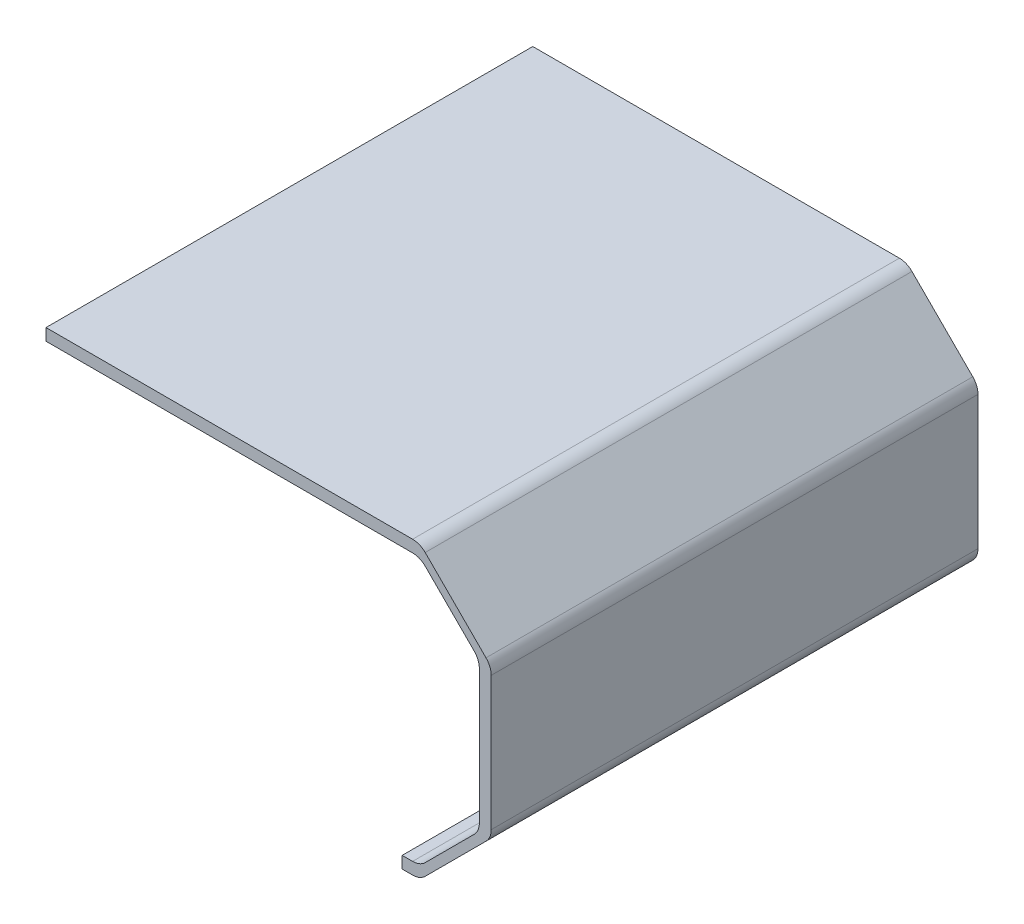
SolidWorks part; units mm, degrees
ref_plane "前视基准面" through (0, 0, 0) normal (0, 0, 1) x (1, 0, 0)
ref_plane "上视基准面" through (0, 0, 0) normal (0, 1, 0) x (1, 0, 0)
ref_plane "右视基准面" through (0, 0, 0) normal (1, 0, 0) x (0, 0, -1)
sketch "草图1" plane through (0, 0, 0) normal (0, 0, 1) x (1, 0, 0)
  line L0 (0, 0) -> (0, 2)
  line L1 (0, 2) -> (3, 2)
  line L5 (-60, 49) -> (3, 49)
  line L7 (0, 0) -> (3, 0)
  line L13 (3, 47) -> (-60, 47)
  line L15 (3, 2) -> (13, 12)
  line L16 (3, 0) -> (15, 12)
  line L17 (13, 37) -> (13, 12)
  line L18 (15, 12) -> (15, 37)
  line L19 (3, 47) -> (13, 37)
  line L20 (3, 49) -> (15, 37)
  line L21 (-60, 49) -> (-60, 47)
  point P5 (0, 0)
extrude "凸台-拉伸1" add sketch "草图1" along normal blind 82
fillet "圆角1" radius 3 8 edges at (3, 0, 41) (15, 12, 41) (15, 37, 41) (3, 49, 41) (3, 2, 41) (13, 12, 41) (13, 37, 41) (3, 47, 41)
